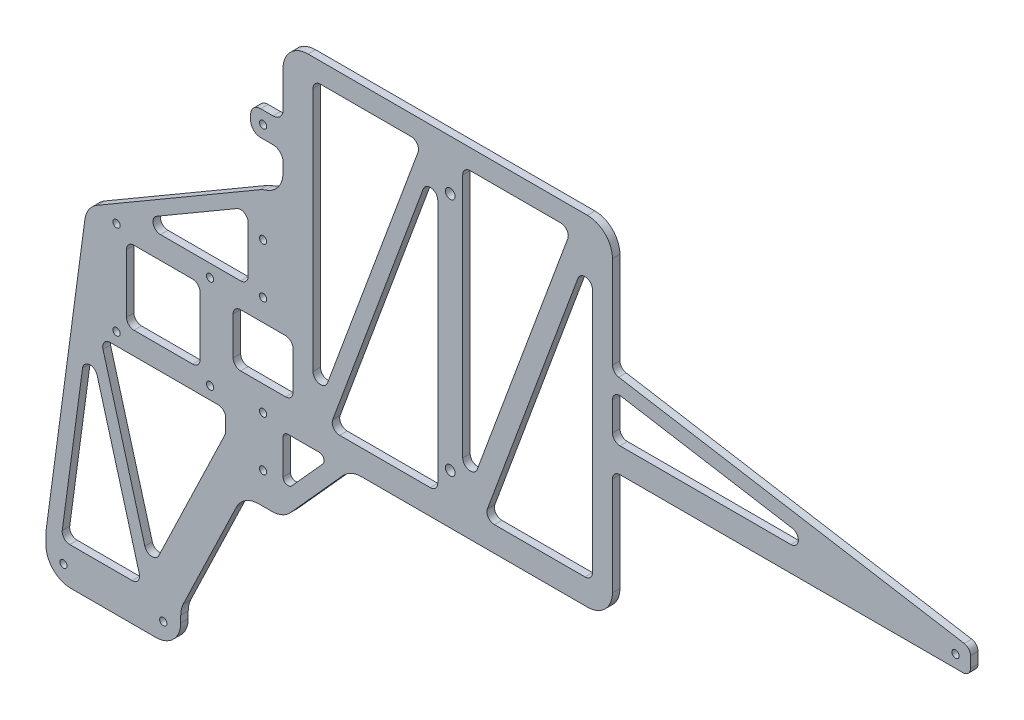
SolidWorks part; units mm, degrees
material "Thornel Mat VMA"
ref_plane "前视基准面" through (0, 0, 0) normal (0, 0, 1) x (1, 0, 0)
ref_plane "上视基准面" through (0, 0, 0) normal (0, 1, 0) x (1, 0, 0)
ref_plane "右视基准面" through (0, 0, 0) normal (1, 0, 0) x (0, 0, -1)
sketch "草图1" plane through (0, 0, 0) normal (0, 0, 1) x (1, 0, 0)
  line L0 (0, 96.1263) -> (0, 64.8807) construction
  line L1 (0, 0) -> (-21.5182, 0) construction
  line L2 (0, 60) -> (-8, 60)
  line L3 (-8, 60) -> (-33, 8)
  line L4 (-33, 8) -> (-33, -7)
  line L5 (-33, -7) -> (-87, -7)
  line L6 (-87, -7) -> (-87, 170) construction
  line L7 (-87, 170) -> (0, 170) construction
  line L8 (140, 226) -> (140, 60) construction
  line L9 (140, 60) -> (0, 60) construction
  line L10 (0, 170) -> (8, 170)
  line L11 (-58.75, 91.25) -> (-21.25, 91.25) construction
  line L12 (-58.75, 91.25) -> (-58.75, 128.75) construction
  line L13 (-58.75, 128.75) -> (-21.25, 128.75) construction
  line L14 (-21.25, 91.25) -> (-21.25, 128.75) construction
  line L15 (-58.75, 91.25) -> (-21.25, 128.75) construction
  line L16 (-58.75, 128.75) -> (-21.25, 91.25) construction
  line L17 (8, 170) -> (8, 226)
  line L18 (8, 226) -> (140, 226)
  line L19 (75, 110) -> (75, 206) construction
  line L20 (0, 60) -> (8, 60)
  line L21 (8, 60) -> (35, 90)
  line L22 (35, 90) -> (140, 90)
  line L23 (140, 90) -> (140, 226)
  line L24 (0, 170) -> (-70.75, 128.75)
  line L25 (20, 100) -> (70, 100)
  line L26 (20, 100) -> (20, 218)
  line L27 (20, 218) -> (70, 218)
  line L28 (70, 100) -> (70, 218)
  line L29 (20, 100) -> (70, 218) construction
  line L30 (20, 218) -> (70, 100) construction
  line L31 (80, 100) -> (132, 100)
  line L32 (80, 100) -> (80, 218)
  line L33 (80, 218) -> (132, 218)
  line L34 (132, 100) -> (132, 218)
  line L35 (80, 100) -> (132, 218) construction
  line L36 (80, 218) -> (132, 100) construction
  line L37 (-70.75, 128.75) -> (-87, 8)
  line L38 (-87, 8) -> (-87, -7)
  line L39 (-15, 77.7506) -> (-48.5339, 8)
  line L40 (-48.5339, 8) -> (-80.9459, 8)
  line L41 (-80.9459, 8) -> (-70.4154, 86.25)
  line L42 (-70.4154, 86.25) -> (-15, 86.25)
  line L43 (-15, 86.25) -> (-15, 77.7506)
  line L44 (-52.2473, 133.75) -> (-6, 160.714)
  line L45 (-54.75, 95.25) -> (-25.25, 95.25)
  line L46 (-54.75, 95.25) -> (-54.75, 124.75)
  line L47 (-54.75, 124.75) -> (-25.25, 124.75)
  line L48 (-25.25, 95.25) -> (-25.25, 124.75)
  line L49 (-54.75, 95.25) -> (-25.25, 124.75) construction
  line L50 (-54.75, 124.75) -> (-25.25, 95.25) construction
  line L51 (-6, 160.714) -> (-6, 133.75)
  line L52 (-6, 133.75) -> (-52.2473, 133.75)
  line L54 (-12, 102.5) -> (12, 102.5)
  line L55 (-12, 102.5) -> (-12, 123.75)
  line L56 (-12, 123.75) -> (12, 123.75)
  line L57 (12, 102.5) -> (12, 123.75)
  line L58 (-12, 102.5) -> (12, 123.75) construction
  line L59 (-12, 123.75) -> (12, 102.5) construction
  circle A0 centre (-80, 0) radius 1.45
  circle A1 centre (-40, 0) radius 1.45
  circle A2 centre (0, 72.5) radius 1.45
  circle A3 centre (0, 92.5) radius 1.45
  circle A4 centre (0, 132.5) radius 1.45
  circle A5 centre (0, 152.5) radius 1.45
  circle A6 centre (-58.75, 128.75) radius 1.45
  circle A7 centre (-21.25, 128.75) radius 1.45
  circle A8 centre (-21.25, 91.25) radius 1.45
  circle A9 centre (-58.75, 91.25) radius 1.45
  circle A10 centre (75, 206) radius 1.95
  circle A11 centre (75, 110) radius 1.95
  point P20 (-40, 110)
  point P44 (45, 159)
  point P50 (106, 159)
  point P59 (-40, 110)
  point P69 (0, 113.125)
  dimension "D1" = 2.9
  dimension "D2" = 72.5
  dimension "D3" = 20
  dimension "D4" = 40
  dimension "D5" = 20
  dimension "D6" = 40
  dimension "D7" = 40
  dimension "D9" = 7
  dimension "D12" = 2.9
  dimension "D23" = 3.9
  dimension "D25" = 3.9
  dimension "D26" = 20
  dimension "D8" = 7
  dimension "D10" = 37.5
  dimension "D11" = 37.5
  dimension "D13" = 140
  dimension "D14" = 60
  dimension "D15" = 8
  dimension "D16" = 7
  dimension "D17" = 15
  dimension "D18" = 110
  dimension "D19" = 40
  dimension "D20" = 8
  dimension "D21" = 96
  dimension "D22" = 90
  dimension "D24" = 20
  dimension "D27" = 75
  dimension "D28" = 60
  dimension "D29" = 8
  dimension "D30" = 35
  dimension "D31" = 10
  dimension "D32" = 12
  dimension "D33" = 8
  dimension "D34" = 5
  dimension "D35" = 5
  dimension "D36" = 8
  dimension "D37" = 10
  dimension "D38" = 8
  dimension "D39" = 15
  dimension "D40" = 12
  dimension "D41" = 6
  dimension "D42" = 14
  dimension "D43" = 15
  dimension "D44" = 5
  dimension "D45" = 15
  dimension "D46" = 4
  dimension "D47" = 4
  dimension "D48" = 5
  dimension "D49" = 5
  dimension "D50" = 6
  dimension "D51" = 8
  dimension "D52" = 10
  dimension "D53" = 10
extrude "凸台-拉伸1" add sketch "草图1" along normal blind 3
sketch "草图2" plane through (0, 0, 0) normal (0, 0, 1) x (1, 0, 0)
  line L0 (70, 218) -> (26.3965, 100)
  line L1 (20, 100) -> (70, 100) construction
  line L2 (26.3965, 100) -> (20, 100)
  line L3 (20, 100) -> (63.6035, 218)
  line L4 (70, 218) -> (20, 218) construction
  line L5 (63.6035, 218) -> (70, 218)
  line L6 (80, 100) -> (123.6035, 218)
  line L7 (132, 218) -> (80, 218) construction
  line L8 (123.6035, 218) -> (132, 218)
  line L9 (132, 218) -> (88.3965, 100)
  line L10 (80, 100) -> (132, 100) construction
  line L11 (88.3965, 100) -> (80, 100)
  line L12 (-48.5339, 8) -> (-70.4154, 86.25)
  line L13 (-70.4154, 86.25) -> (-65.2236, 86.25)
  line L14 (-15, 86.25) -> (-70.4154, 86.25) construction
  line L15 (-65.2236, 86.25) -> (-45.2514, 14.8277)
  line L16 (-48.5339, 8) -> (-15, 77.7506) construction
  line L17 (-45.2514, 14.8277) -> (-48.5339, 8)
  dimension "D1" = 6
  dimension "D2" = 5
extrude "凸台-拉伸2" add sketch "草图2" along normal up to surface (3 mm away) up to face at (76.95, 206, 3)
fillet "圆角1" radius 3 30 edges at (-12, 123.75, 1.5) (-12, 102.5, 1.5) (12, 102.5, 1.5) (12, 123.75, 1.5) (-6, 160.714, 1.5) (-52.2473, 133.75, 1.5) (-54.75, 124.75, 1.5) (-54.75, 95.25, 1.5) (-25.25, 95.25, 1.5) (-25.25, 124.75, 1.5) (-65.2236, 86.25, 1.5) (-45.2514, 14.8277, 1.5) (-15, 77.7506, 1.5) (-15, 86.25, 1.5) (88.3965, 100, 1.5) (132, 100, 1.5) (132, 218, 1.5) (26.3965, 100, 1.5) (70, 100, 1.5) (70, 218, 1.5) (-80.9459, 8, 1.5) (-48.5339, 8, 1.5) (-70.4154, 86.25, 1.5) (80, 218, 1.5) (80, 100, 1.5) (123.6035, 218, 1.5) (20, 218, 1.5) (20, 100, 1.5) (63.6035, 218, 1.5) (-6, 133.75, 1.5)
fillet "圆角2" radius 10 1 edges at (8, 170, 1.5)
fillet "圆角3" radius 10 12 edges at (-8, 60, 1.5) (-33, 8, 1.5) (-33, -7, 1.5) (-87, -7, 1.5) (-87, 8, 1.5) (0, 170, 1.5) (8, 226, 1.5) (140, 226, 1.5) (140, 90, 1.5) (35, 90, 1.5) (8, 60, 1.5) (-70.75, 128.75, 1.5)
sketch "草图3" plane through (0, 0, 0) normal (0, 0, 1) x (1, 0, 0)
  line L0 (8, 216) -> (8, 179.798) construction
  line L1 (8, 197.5) -> (-5, 197.5)
  line L2 (8, 197.5) -> (8, 187.5)
  line L3 (8, 187.5) -> (-5, 187.5)
  line L4 (-5, 197.5) -> (-5, 187.5)
  circle A0 centre (0, 192.5) radius 1.45
  circle A1 centre (0, 152.5) radius 1.45 construction
  dimension "D1" = 2.9
  dimension "D2" = 40
  dimension "D4" = 5
  dimension "D3" = 5
  dimension "D5" = 5
extrude "凸台-拉伸3" add sketch "草图3" along normal up to surface (3 mm away) up to face at (35.0366, 182.7318, 3)
fillet "圆角4" radius 4 4 edges at (8, 187.5, 1.5) (-5, 187.5, 1.5) (8, 197.5, 1.5) (-5, 197.5, 1.5)
sketch "草图4" plane through (0, 0, 0) normal (0, 0, 1) x (1, 0, 0)
  line L0 (140, 152.5) -> (283.5, 152.5)
  line L1 (140, 100) -> (140, 216) construction
  line L2 (283.5, 152.5) -> (283.5, 142.5)
  line L3 (283.5, 142.5) -> (140, 142.5)
  line L4 (140, 152.5) -> (140, 142.5)
  circle A0 centre (277.5, 147.5) radius 1.45
  dimension "D3" = 2.9
  dimension "D4" = 5
  dimension "D5" = 5
  dimension "D6" = 6
  dimension "D1" = 277.5
  dimension "D2" = 147.5
extrude "凸台-拉伸4" add sketch "草图4" along normal up to surface (3 mm away) up to face at (35.0366, 182.7318, 3)
sketch "草图5" plane through (0, 0, 0) normal (0, 0, 1) x (1, 0, 0)
  line L6 (283.5, 152.5) -> (140, 176.5)
  line L7 (140, 152.5) -> (140, 216) construction
  line L8 (140, 176.5) -> (140, 170.5)
  line L9 (140, 170.5) -> (247.625, 152.5)
  line L10 (283.5, 152.5) -> (140, 152.5) construction
  line L11 (247.625, 152.5) -> (283.5, 152.5)
  dimension "D1" = 24
  dimension "D2" = 6
extrude "凸台-拉伸5" add sketch "草图5" along normal up to surface (3 mm away) up to face at (35.0366, 182.7318, 3)
fillet "圆角5" radius 3 7 edges at (140, 176.5, 1.5) (283.5, 152.5, 1.5) (140, 142.5, 1.5) (140, 152.5, 1.5) (247.625, 152.5, 1.5) (140, 170.5, 1.5) (283.5, 142.5, 1.5)
sketch "草图6" plane through (0, 0, 3) normal (0, 0, 1) x (1, 0, 0)
  line L0 (8, 90) -> (8, 68.9691)
  line L1 (8, 68.9691) -> (26.9278, 90)
  line L2 (26.9278, 90) -> (8, 90)
  line L3 (10.9793, 63.3104) -> (32.0207, 86.6896) construction
  line L4 (30.7034, 100) -> (67, 100) construction
  circle A0 centre (0, 72.5) radius 1.45 construction
  dimension "D1" = 6
  dimension "D2" = 10
  dimension "D3" = 8
extrude "切除-拉伸1" cut sketch "草图6" against normal through all
fillet "圆角6" radius 2 3 edges at (8, 68.9691, 1.5) (26.9278, 90, 1.5) (8, 90, 1.5)
